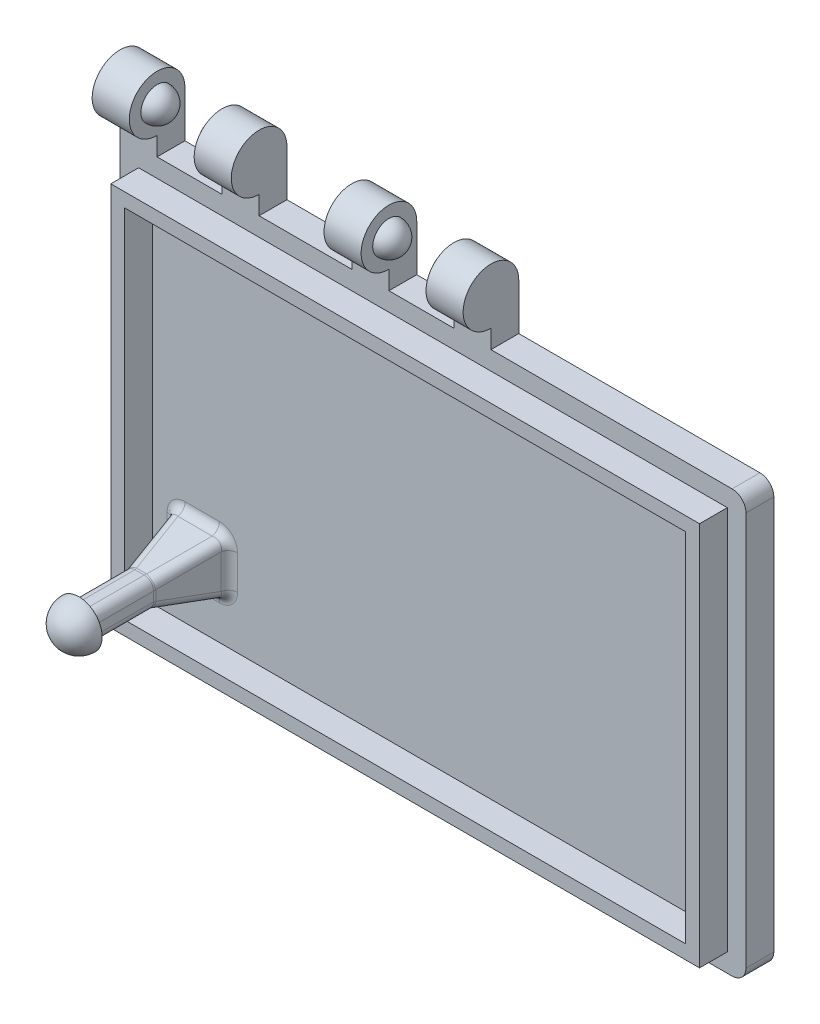
SolidWorks part; units mm, degrees
ref_plane "Front Plane" through (0, 0, 0) normal (0, 0, 1) x (1, 0, 0)
ref_plane "Top Plane" through (0, 0, 0) normal (0, 1, 0) x (1, 0, 0)
ref_plane "Right Plane" through (0, 0, 0) normal (1, 0, 0) x (0, 0, -1)
sketch "Sketch1" plane through (0, 0, 0) normal (0, 0, 1) x (1, 0, 0)
  line L1 (-33.75, -22.75) -> (33.75, -22.75)
  line L2 (-33.75, -22.75) -> (-33.75, 22.75)
  line L3 (-33.75, 22.75) -> (33.75, 22.75)
  line L4 (33.75, -22.75) -> (33.75, 22.75)
  line L5 (-33.75, -22.75) -> (33.75, 22.75) construction
  line L6 (-33.75, 22.75) -> (33.75, -22.75) construction
  point P0 (0, 0)
  dimension "D1" = 67.5
  dimension "D2" = 45.5
extrude "Boss-Extrude1" add sketch "Sketch1" along normal blind 3
sketch "Sketch23" plane through (0, 0, 3) normal (0, 0, 1) x (1, 0, 0)
  line L0 (-24.875, -22.75) -> (-33.75, -22.75) construction
  line L2 (-24.875, -22.75) -> (-24.875, -11.735) construction
  line L4 (-27.875, -8.735) -> (-21.875, -8.735)
  line L5 (-27.875, -8.735) -> (-27.875, -14.735)
  line L6 (-27.875, -14.735) -> (-21.875, -14.735)
  line L7 (-21.875, -8.735) -> (-21.875, -14.735)
  line L8 (-27.875, -8.735) -> (-21.875, -14.735) construction
  line L9 (-27.875, -14.735) -> (-21.875, -8.735) construction
  dimension "D1" = 8.875
  dimension "D2" = 11.015
  dimension "D3" = 6
  dimension "D4" = 6
sketch "Sketch20" plane through (0, 22.75, 0) normal (0, 1, 0) x (1, 0, 0)
  line L0 (-33.75, -3) -> (-26.25, -3) construction
  line L1 (33.75, -3) -> (-33.75, -3) construction
  line L2 (-26.25, -3) -> (-26.25, 0) construction
  line L3 (33.75, 0) -> (-33.75, 0) construction
  dimension "D1" = 7.5
ref_plane "Plane1" through (-26.25, 0, 0) normal (1, 0, 0) x (0, 0, -1)
sketch "Sketch22" plane through (0, 22.75, 0) normal (0, 1, 0) x (1, 0, 0)
  line L0 (-33.75, 0) -> (-13.75, 0) construction
  line L1 (-13.75, 0) -> (-13.75, -3) construction
  line L2 (33.75, -3) -> (-33.75, -3) construction
  dimension "D1" = 20
ref_plane "Plane2" through (-13.75, 0, 0) normal (1, 0, 0) x (0, 0, -1)
sketch "Sketch10" plane through (-33.75, 0, 0) normal (-1, 0, 0) x (0, 0, 1)
  line L0 (3, 22.75) -> (3, 27.75) construction
  line L3 (0, 27.75) -> (0, 22.75)
  line L4 (0, 22.75) -> (3, 22.75)
  line L5 (3, 22.75) -> (3, 24.75)
  arc A1 (3, 24.75) -> (0, 27.75) centre (3, 27.75) ccw
  dimension "D1" = 5
  dimension "D2" = 6
extrude "Boss-Extrude4" add sketch "Sketch10" against normal blind 4
sketch "Sketch17" plane through (-29.75, 0, 0) normal (1, 0, 0) x (0, 0, -1)
  circle A0 centre (-3, 27.75) radius 1.75
  dimension "D1" = 3.5
sketch "Sketch9" plane through (0, 0, 3) normal (0, 0, 1) x (1, 0, 0)
  line L0 (-33.75, -22.75) -> (33.75, -22.75) construction
  line L2 (-31.74, 20.74) -> (-30.24, 20.74)
  line L4 (-31.74, 20.74) -> (-31.74, -20.74)
  line L5 (33.75, -22.75) -> (33.75, 22.75) construction
  line L6 (-31.74, -20.74) -> (-30.24, -20.74)
  line L7 (-30.24, 19.24) -> (-30.24, -19.24)
  line L8 (33.75, 22.75) -> (-29.75, 22.75) construction
  line L9 (33.75, 22.75) -> (-29.75, 22.75) construction
  line L10 (-33.75, 24.75) -> (-33.75, -22.75) construction
  line L23 (-30.24, 20.74) -> (31.74, 20.74)
  line L25 (-30.24, 19.24) -> (30.24, 19.24)
  line L26 (31.74, 20.74) -> (31.74, 19.24)
  line L28 (31.74, 19.24) -> (31.74, -20.74)
  line L29 (31.74, -20.74) -> (30.24, -20.74)
  line L30 (30.24, 19.24) -> (30.24, -19.24)
  line L31 (-30.24, -20.74) -> (30.24, -20.74)
  line L33 (-30.24, -19.24) -> (30.24, -19.24)
  dimension "D1" = 2.01
  dimension "D2" = 2.01
  dimension "D3" = 1.5
  dimension "D4" = 2.01
  dimension "D5" = 1.5
  dimension "D7" = 1.5
  dimension "D8" = 2.01
  dimension "D10" = 1.5
  dimension "D11" = 1.5
extrude "Boss-Extrude3" add sketch "Sketch9" along normal blind 3
fillet "Fillet6" radius 1.5 3 edges at (-33.75, -22.75, 1.5) (33.75, -22.75, 1.5) (33.75, 22.75, 1.5)
sketch "Sketch18" plane through (-29.75, 0, 0) normal (1, 0, 0) x (0, 0, -1)
  line L0 (-3, 29.5) -> (-3, 26)
  arc A0 (-3, 26) -> (-3, 29.5) centre (-3, 27.75) ccw
  dimension "D1" = 3.5
revolve "Revolve1" add sketch "Sketch18" angle 180 about L0
mirror "Mirror1" about plane through (-26.25, 0, 0) normal (1, 0, 0) of "Revolve1", "Boss-Extrude4"
mirror "Mirror2" about plane through (-13.75, 0, 0) normal (1, 0, 0) of "Mirror1"
ref_plane "Plane3" through (0, 0, 9.65) normal (0, 0, 1) x (1, 0, 0)
sketch "Sketch25" plane through (0, 0, 9.65) normal (0, 0, 1) x (1, 0, 0)
  line L0 (-27.875, -8.735) -> (-21.875, -14.735) construction
  line L2 (-26.375, -10.235) -> (-23.375, -10.235)
  line L3 (-26.375, -10.235) -> (-26.375, -13.235)
  line L4 (-26.375, -13.235) -> (-23.375, -13.235)
  line L5 (-23.375, -10.235) -> (-23.375, -13.235)
  line L6 (-26.375, -10.235) -> (-23.375, -13.235) construction
  line L7 (-26.375, -13.235) -> (-23.375, -10.235) construction
  point P4 (-24.875, -11.735)
  dimension "D1" = 3
  dimension "D2" = 3
loft "Loft2" add profiles "Sketch23", "Sketch25" connector at (-27.875, -14.735, 3) connector at (-26.375, -13.235, 9.65)
sketch "Sketch27" plane through (0, 0, 9.65) normal (0, 0, 1) x (1, 0, 0)
  line L1 (-26.375, -10.235) -> (-23.375, -10.235)
  line L2 (-26.375, -10.235) -> (-26.375, -13.235)
  line L3 (-26.375, -13.235) -> (-23.375, -13.235)
  line L4 (-23.375, -10.235) -> (-23.375, -13.235)
extrude "Boss-Extrude5" add sketch "Sketch27" along normal blind 6.65
sketch "Sketch28" plane through (0, 0, 16.3) normal (0, 0, 1) x (1, 0, 0)
  line L0 (-26.375, -10.235) -> (-23.375, -13.235) construction
  line L1 (-24.875, -9.235) -> (-24.875, -14.235)
  arc A0 (-24.875, -14.235) -> (-24.875, -9.235) centre (-24.875, -11.735) ccw
  dimension "D1" = 5
revolve "Revolve3" add sketch "Sketch28" angle 180 about L1
fillet "Fillet7" radius 1 16 edges
